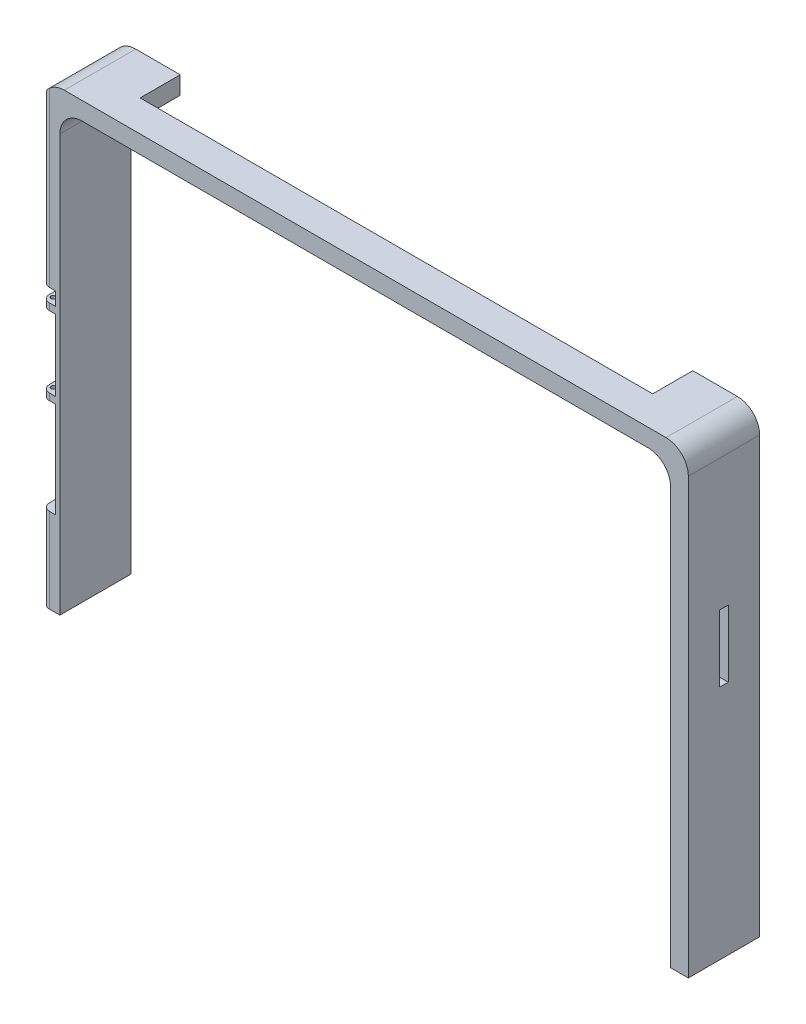
SolidWorks part; units mm, degrees
ref_plane "前视基准面" through (0, 0, 0) normal (0, 0, 1) x (1, 0, 0)
ref_plane "上视基准面" through (0, 0, 0) normal (0, 1, 0) x (1, 0, 0)
ref_plane "右视基准面" through (0, 0, 0) normal (1, 0, 0) x (0, 0, -1)
sketch "草图1" plane through (0, 0, 0) normal (0, 0, 1) x (1, 0, 0)
  line L0 (145.3333, -27.0486) -> (153.3333, -27.0486)
  line L1 (-126.6667, 177.9514) -> (143.3333, 177.9514)
  line L2 (-136.6667, 167.9514) -> (-136.6667, -27.0486)
  line L3 (-136.6667, -27.0486) -> (-128.6667, -27.0486)
  line L4 (153.3333, 167.9514) -> (153.3333, -27.0486)
  line L6 (-128.6667, -27.0486) -> (-128.6667, 159.9514)
  line L7 (-118.6667, 169.9514) -> (135.3333, 169.9514)
  line L8 (145.3333, -27.0486) -> (145.3333, 159.9514)
  arc A0 (143.3333, 177.9514) -> (153.3333, 167.9514) centre (143.3333, 167.9514) cw
  arc A1 (-126.6667, 177.9514) -> (-136.6667, 167.9514) centre (-126.6667, 167.9514) ccw
  arc A2 (135.3333, 169.9514) -> (145.3333, 159.9514) centre (135.3333, 159.9514) cw
  arc A3 (-128.6667, 159.9514) -> (-118.6667, 169.9514) centre (-118.6667, 159.9514) cw
  point P6 (153.3333, 177.9514)
  point P9 (-136.6667, 177.9514)
  dimension "D3" = 10
  dimension "D7" = 10
  dimension "D1" = 205
  dimension "D2" = 290
  dimension "D4" = 8
  dimension "D5" = 8
  dimension "D6" = 8
extrude "凸台-拉伸1" add sketch "草图1" along normal blind 32
sketch "草图2" plane through (0, 0, 0) normal (0, 0, -1) x (-1, 0, 0)
  line L0 (136.6667, 167.9514) -> (136.6667, -27.0486) construction
  line L1 (-143.3333, 177.9514) -> (126.6667, 177.9514) construction
  line L2 (-153.3333, -27.0486) -> (-153.3333, 167.9514) construction
  circle A0 centre (132.6667, 127.9514) radius 2.05
  circle A1 centre (132.6667, 24.9514) radius 2.05
  circle A2 centre (-149.3333, 127.9514) radius 2.05
  circle A3 centre (-149.3333, 24.9514) radius 2.05
  circle A4 centre (-135.3333, 173.9514) radius 2.05
  circle A5 centre (-8.3333, 173.9514) radius 2.05
  circle A6 centre (118.6667, 173.9514) radius 2.05
  dimension "D1" = 4.1
  dimension "D6" = 2
  dimension "D7" = 4.1
  dimension "D2" = 4
  dimension "D3" = 50
  dimension "D5" = 4
  dimension "D8" = 18
  dimension "D9" = 4
  dimension "D4" = 2
  dimension "D10" = 3
extrude "切除-拉伸1" cut sketch "草图2" against normal blind 5.1
sketch "草图3" plane through (0, 177.9514, 0) normal (0, 1, 0) x (1, 0, 0)
  line L0 (143.3333, 0) -> (-126.6667, 0) construction
  line L1 (-106.6667, 0) -> (123.3333, 0)
  line L2 (-106.6667, 0) -> (-106.6667, -18)
  line L3 (-106.6667, -18) -> (123.3333, -18)
  line L4 (123.3333, 0) -> (123.3333, -18)
  line L5 (-136.6667, -32) -> (-136.6667, 0) construction
  line L6 (153.3333, -32) -> (153.3333, 0) construction
  dimension "D1" = 30
  dimension "D2" = 30
  dimension "D3" = 18
extrude "切除-拉伸2" cut sketch "草图3" against normal blind 8
sketch "草图4" plane through (-136.6667, 0, 0) normal (-1, 0, 0) x (0, 0, 1)
  line L0 (32, 167.9514) -> (32, -27.0486) construction
  line L1 (32, 88.9514) -> (26, 88.9514)
  line L2 (32, 88.9514) -> (32, 56.9514)
  line L3 (32, 56.9514) -> (26, 56.9514)
  line L4 (26, 88.9514) -> (26, 56.9514)
  line L6 (32, 177.9514) -> (0, 177.9514) construction
  line L7 (32, 97.9514) -> (26, 97.9514)
  line L8 (32, 97.9514) -> (32, 91.9514)
  line L9 (32, 91.9514) -> (26, 91.9514)
  line L10 (26, 97.9514) -> (26, 91.9514)
  line L12 (32, 53.9514) -> (26, 53.9514)
  line L13 (32, 53.9514) -> (32, 10.9514)
  line L14 (32, 10.9514) -> (26, 10.9514)
  line L15 (26, 53.9514) -> (26, 10.9514)
  dimension "D1" = 80
  dimension "D2" = 32
  dimension "D3" = 6
  dimension "D4" = 6
  dimension "D5" = 6
  dimension "D6" = 3
  dimension "D7" = 6
  dimension "D8" = 43
  dimension "D9" = 3
extrude "切除-拉伸3" cut sketch "草图4" against normal blind 6
sketch "草图5" plane through (0, 53.9514, 0) normal (0, -1, 0) x (1, 0, 0)
  line L0 (-130.6667, 32) -> (-136.6667, 32) construction
  line L1 (-136.6667, 32) -> (-136.6667, 26) construction
  circle A0 centre (-134.6667, 29) radius 1
  dimension "D1" = 2
  dimension "D2" = 3
  dimension "D3" = 2
extrude "切除-拉伸4" cut sketch "草图5" against normal blind 38
sketch "草图6" plane through (145.3333, 0, 0) normal (-1, 0, 0) x (0, 0, 1)
  line L0 (32, 159.9514) -> (0, 159.9514) construction
  line L1 (14.0787, 108.9514) -> (18.0787, 108.9514)
  line L2 (14.0787, 108.9514) -> (14.0787, 78.9514)
  line L3 (14.0787, 78.9514) -> (18.0787, 78.9514)
  line L4 (18.0787, 108.9514) -> (18.0787, 78.9514)
  dimension "D1" = 30
  dimension "D2" = 4
  dimension "D3" = 51
extrude "切除-拉伸5" cut sketch "草图6" against normal through all
chamfer "倒角1" distance 0.3 distance2 8 1 edges at (145.3333, 93.9514, 18.0787) first distance on face at (145.3333, 93.9514, 16.0787)
sketch "草图7" plane through (0, 177.9514, 0) normal (0, 1, 0) x (1, 0, 0)
  line L0 (-136.6667, -28.7) -> (-136.6667, -32)
  line L1 (-136.6667, -32) -> (-136.6667, 0) construction
  line L2 (-136.6667, -32) -> (-133.3667, -32)
  line L3 (-136.6667, -32) -> (-126.6667, -32) construction
  arc A0 (-136.6667, -28.7) -> (-133.3667, -32) centre (-133.3667, -28.7) ccw
  dimension "D1" = 3.3
  dimension "D2" = 3.3
extrude "切除-拉伸6" cut sketch "草图7" against normal through all
